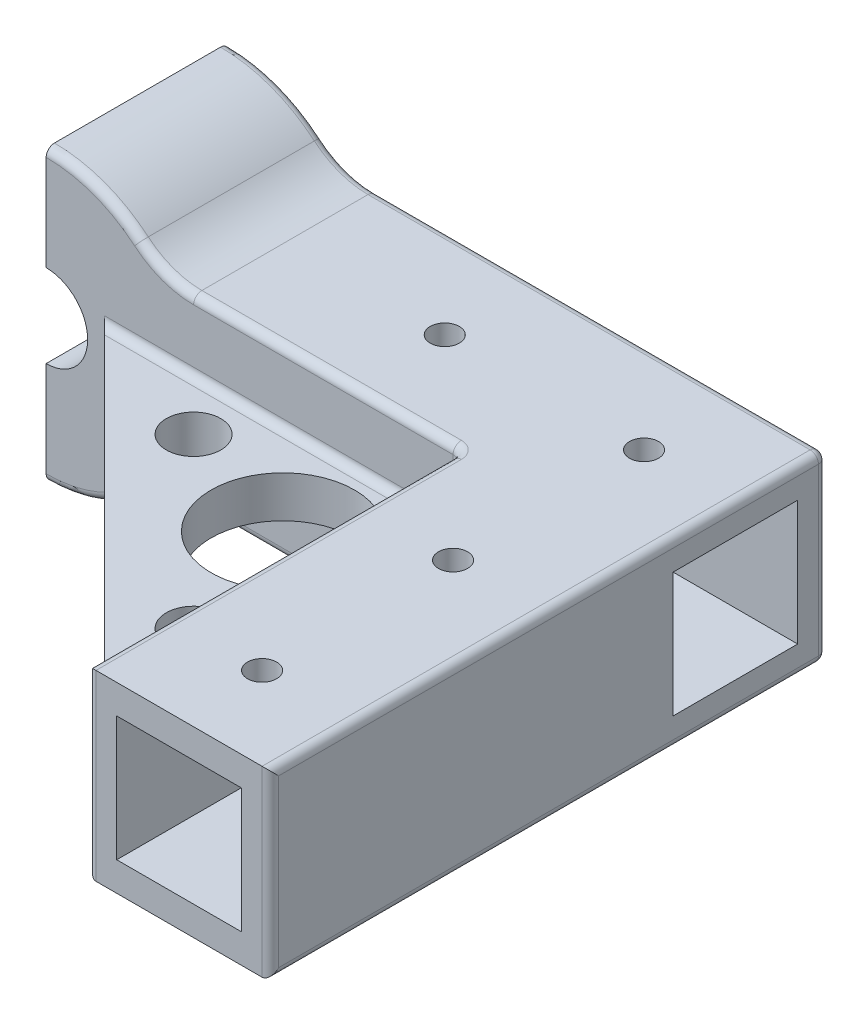
SolidWorks part; units mm, degrees
ref_plane "Front Plane" through (0, 0, 0) normal (0, 0, 1) x (1, 0, 0)
ref_plane "Top Plane" through (0, 0, 0) normal (0, 1, 0) x (1, 0, 0)
ref_plane "Right Plane" through (0, 0, 0) normal (1, 0, 0) x (0, 0, -1)
sketch "Sketch1" plane through (0, 0, 0) normal (0, 0, 1) x (1, 0, 0)
  line L0 (41.5599, 4.1233) -> (41.5599, -17.8767) construction
  line L1 (5.1706, 4.1233) -> (63.5599, 4.1233)
  line L2 (-8.4401, 7.6443) -> (-8.4401, -1.8767)
  line L3 (5.1706, -17.8767) -> (63.5599, -17.8767)
  line L4 (63.5599, 4.1233) -> (63.5599, -17.8767)
  line L5 (-8.4401, -11.8767) -> (-8.4401, -14.3557)
  line L6 (-8.4401, -14.3557) -> (-8.4401, -24.3767)
  line L7 (-8.4401, 7.6443) -> (-8.4401, 10.6233)
  arc A0 (-8.4401, -11.8767) -> (-8.4401, -1.8767) centre (-8.4401, -6.8767) ccw
  arc A1 (5.1706, 4.1233) -> (-8.4401, 10.6233) centre (-8.4401, -6.8767) ccw
  arc A2 (-8.4401, -24.3767) -> (5.1706, -17.8767) centre (-8.4401, -6.8767) ccw
  dimension "D4" = 10
  dimension "D5" = 35
  dimension "D1" = 22
  dimension "D2" = 50
  dimension "D3" = 22
  dimension "D6" = 11
extrude "Boss-Extrude1" add sketch "Sketch1" along normal blind 22
sketch "Sketch2" plane through (0, 0, 22) normal (0, 0, 1) x (1, 0, 0)
  line L0 (5.1706, -17.8767) -> (63.5599, -17.8767) construction
  line L1 (63.5599, 4.1233) -> (41.5599, 4.1233)
  line L2 (63.5599, 4.1233) -> (63.5599, -17.8767)
  line L3 (63.5599, -17.8767) -> (41.5599, -17.8767)
  line L4 (41.5599, 4.1233) -> (41.5599, -17.8767)
  dimension "D1" = 22
extrude "Boss-Extrude2" add sketch "Sketch2" along normal blind 45
sketch "Sketch3" plane through (0, 0, 67) normal (0, 0, 1) x (1, 0, 0)
  line L0 (63.5599, -17.8767) -> (63.5599, 4.1233) construction
  line L1 (45.0599, 0.6233) -> (60.0599, 0.6233)
  line L2 (45.0599, 0.6233) -> (45.0599, -14.3767)
  line L3 (45.0599, -14.3767) -> (60.0599, -14.3767)
  line L4 (60.0599, 0.6233) -> (60.0599, -14.3767)
  line L5 (63.5599, 4.1233) -> (41.5599, 4.1233) construction
  dimension "D1" = 15
  dimension "D2" = 3.5
  dimension "D3" = 15
  dimension "D4" = 3.5
extrude "Cut-Extrude1" cut sketch "Sketch3" against normal offset from surface (43 mm away) 2 up to face at (8.2716, -5.5017, 22)
sketch "Sketch4" plane through (63.5599, 0, 0) normal (1, 0, 0) x (0, 0, -1)
  line L0 (-67, 4.1233) -> (0, 4.1233) construction
  line L1 (-3.5, 0.6233) -> (-18.5, 0.6233)
  line L2 (-3.5, 0.6233) -> (-3.5, -14.3767)
  line L3 (-3.5, -14.3767) -> (-18.5, -14.3767)
  line L4 (-18.5, 0.6233) -> (-18.5, -14.3767)
  line L5 (0, -17.8767) -> (0, 4.1233) construction
  dimension "D1" = 15
  dimension "D2" = 15
  dimension "D3" = 3.5
  dimension "D4" = 3.5
extrude "Cut-Extrude2" cut sketch "Sketch4" against normal blind 45
ref_plane "Plane1" through (0, -6.8767, 0) normal (0, 1, 0) x (1, 0, 0)
sketch "Sketch6" plane through (0, -6.8767, 0) normal (0, 1, 0) x (1, 0, 0)
  line L0 (-1.4401, -22) -> (41.5599, -65)
  line L1 (41.5599, -22) -> (5.1706, -22) construction
  line L2 (41.5599, -67) -> (41.5599, -22) construction
  line L3 (41.5599, -65) -> (41.5599, -22)
  line L4 (41.5599, -22) -> (-1.4401, -22)
  line L5 (-3.4401, -22) -> (-3.4401, 0) construction
  dimension "D1" = 2
  dimension "D2" = 45
extrude "Boss-Extrude3" add sketch "Sketch6" along normal blind 2.5 and the other way blind 2.5
fillet "Fillet1" radius 10 2 edges at (5.1706, -17.8767, 11) (5.1706, 4.1233, 11)
sketch "Sketch5" plane through (-8.4401, 0, 0) normal (-1, 0, 0) x (0, 0, 1)
  line L0 (0, 4.3733) -> (22, 4.3733) construction
  line L1 (0, 10.6233) -> (0, -1.8767) construction
  line L2 (22, 10.6233) -> (22, -1.8767) construction
  line L3 (0, -18.1267) -> (22, -18.1267) construction
  line L4 (0, -11.8767) -> (0, -24.3767) construction
  line L5 (22, -11.8767) -> (22, -24.3767) construction
  circle A1 centre (11, 4.3733) radius 1.75
  circle A3 centre (11, -18.1267) radius 1.75
  dimension "D1" = 3.5
  dimension "D4" = 11
  dimension "D5" = 11
extrude "Cut-Extrude3" cut sketch "Sketch5" against normal blind 8
sketch "Sketch8" plane through (0, -17.8767, 0) normal (0, -1, 0) x (1, 0, 0)
  line L0 (18.5599, 11) -> (63.5599, 11) construction
  line L1 (18.5599, 18.5) -> (18.5599, 3.5) construction
  line L2 (63.5599, 67) -> (63.5599, 0) construction
  line L3 (52.5599, 24) -> (52.5599, 67) construction
  line L4 (60.0599, 24) -> (45.0599, 24) construction
  line L5 (41.5599, 67) -> (63.5599, 67) construction
  circle A0 centre (28.5599, 11) radius 1.75
  circle A1 centre (52.5599, 11) radius 1.75
  circle A2 centre (52.5599, 34) radius 1.75
  circle A3 centre (52.5599, 57) radius 1.75
  dimension "D1" = 3.5
  dimension "D2" = 10
  dimension "D3" = 10
  dimension "D4" = 10
extrude "Cut-Extrude5" cut sketch "Sketch8" against normal up to surface (22 mm away) up to face at (40.8321, 4.1233, 33.4167)
sketch "Sketch9" plane through (0, 0, 0) normal (0, 0, -1) x (-1, 0, 0)
  line L0 (-61.5599, -12.8767) -> (-9.3152, -12.8767) construction
  line L2 (-9.3152, -17.8767) -> (-63.5599, -17.8767) construction
  line L3 (-63.5599, -17.8767) -> (-63.5599, 4.1233) construction
  text T0 "ALFR3D" font "Murder Of Mayday" height 12
  dimension "D1" = 5
  dimension "D2" = 2
extrude "Cut-Extrude6" cut sketch "Sketch9" against normal blind 1.5
sketch "Sketch10" plane through (0, -9.3767, 0) normal (0, -1, 0) x (1, 0, 0)
  line L0 (41.5599, 22) -> (20.0599, 43.5) construction
  line L1 (-1.4401, 22) -> (41.5599, 65) construction
  line L2 (41.5599, 67) -> (41.5599, 22) construction
  line L3 (41.5599, 22) -> (-1.4401, 22) construction
  circle A0 centre (30.8099, 32.75) radius 8.6369
  circle A1 centre (35.5599, 48.25) radius 3.2807
  circle A2 centre (15.3099, 28) radius 3.2807
  dimension "D1" = 6
  dimension "D2" = 6
  dimension "D3" = 15.5
  dimension "D4" = 15.5
extrude "Cut-Extrude7" cut sketch "Sketch10" against normal up to surface (5 mm away) up to face at (27.2266, -4.3767, 36.3333)
fillet "Fillet2" radius 1 25 edges at (-2.424, 9.5567, 22) (5.8774, 4.7328, 22) (-2.424, -23.3101, 22) (5.8774, -18.4862, 22) (-2.424, -23.3101, 0) (5.8774, -18.4862, 0) (-2.424, 9.5567, 0) (5.8774, 4.7328, 0) (41.5599, -6.8767, 67) (63.5599, -6.8767, 67) (20.0599, -9.3767, 22) (41.5599, -9.3767, 43.5) (20.0599, -4.3767, 22) (41.5599, -4.3767, 43.5) (63.5599, 4.1233, 33.5) (63.5599, -17.8767, 33.5) (63.5599, -6.8767, 0) (36.4376, -17.8767, 0) (36.4376, 4.1233, 0)
sketch "Sketch11" plane through (-8.4401, 0, 0) normal (-1, 0, 0) x (0, 0, 1)
  line L1 (12.5877, 7.1233) -> (9.4123, 7.1233)
  line L2 (9.4123, 7.1233) -> (7.8246, 4.3733)
  line L3 (7.8246, 4.3733) -> (9.4123, 1.6233)
  line L4 (9.4123, 1.6233) -> (12.5877, 1.6233)
  line L5 (12.5877, 1.6233) -> (14.1754, 4.3733)
  line L6 (14.1754, 4.3733) -> (12.5877, 7.1233)
  line L7 (21, 10.6233) -> (1, 10.6233) construction
  line L8 (14.1754, -18.1267) -> (12.5877, -15.3767)
  line L9 (12.5877, -15.3767) -> (9.4123, -15.3767)
  line L10 (9.4123, -15.3767) -> (7.8246, -18.1267)
  line L11 (7.8246, -18.1267) -> (9.4123, -20.8767)
  line L12 (9.4123, -20.8767) -> (12.5877, -20.8767)
  line L13 (12.5877, -20.8767) -> (14.1754, -18.1267)
  circle A0 centre (11, 4.3733) radius 2.75 construction
  circle A1 centre (11, -18.1267) radius 2.75 construction
  dimension "D1" = 5.5
extrude "Cut-Extrude8" cut sketch "Sketch11" against normal blind 3
